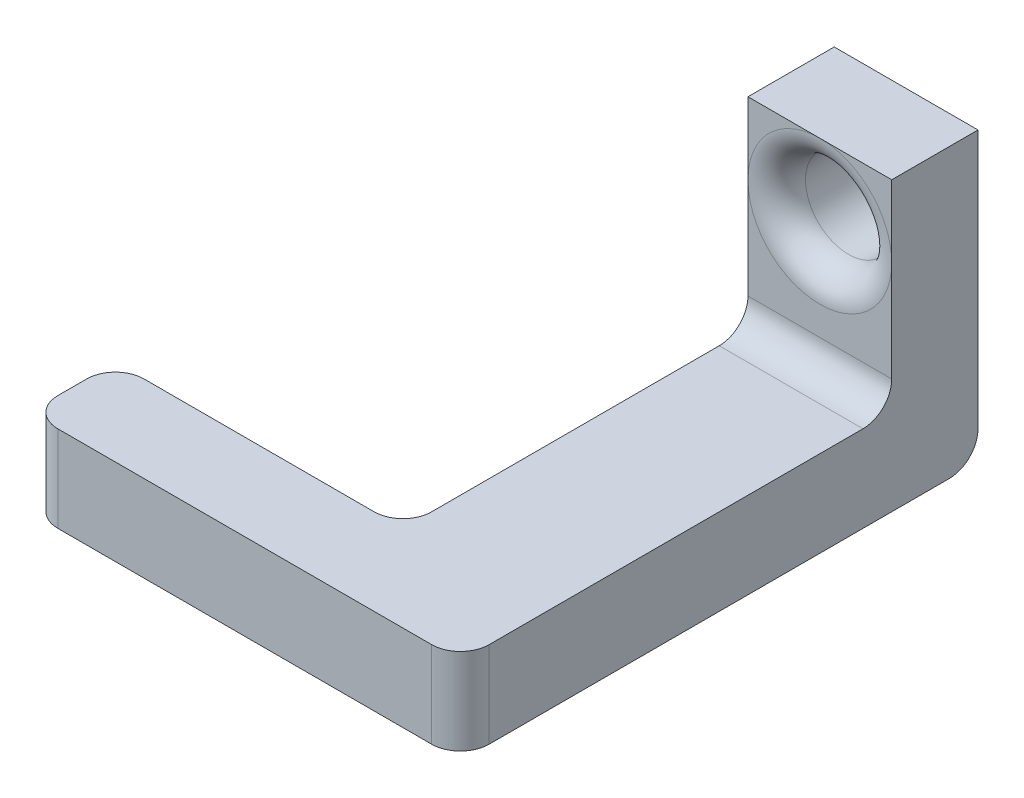
SolidWorks part; units mm, degrees
ref_plane "Front Plane" through (0, 0, 0) normal (0, 0, 1) x (1, 0, 0)
ref_plane "Top Plane" through (0, 0, 0) normal (0, 1, 0) x (1, 0, 0)
ref_plane "Right Plane" through (0, 0, 0) normal (1, 0, 0) x (0, 0, -1)
sketch "Sketch1" plane through (0, 0, 0) normal (0, 0, 1) x (1, 0, 0)
  line L1 (-6.901, 8.8281) -> (-1.901, 8.8281)
  line L2 (-6.901, 8.8281) -> (-6.901, -1.1719)
  line L3 (-6.901, -1.1719) -> (-1.901, -1.1719)
  line L4 (-1.901, 8.8281) -> (-1.901, -1.1719)
  circle A0 centre (-4.401, 6.3281) radius 1.5
  dimension "D3" = 3
  dimension "D4" = 2.5
  dimension "D1" = 5
  dimension "D2" = 10
extrude "Boss-Extrude1" add sketch "Sketch1" along normal blind 3
sketch "Sketch2" plane through (0, 0, 3) normal (0, 0, 1) x (1, 0, 0)
  line L0 (-1.901, -1.1719) -> (-1.901, 8.8281) construction
  line L1 (-6.901, -1.1719) -> (-1.901, -1.1719)
  line L2 (-6.901, -1.1719) -> (-6.901, 1.8281)
  line L3 (-6.901, 1.8281) -> (-1.901, 1.8281)
  line L4 (-1.901, -1.1719) -> (-1.901, 1.8281)
  dimension "D1" = 3
extrude "Boss-Extrude2" add sketch "Sketch2" along normal blind 15
sketch "Sketch3" plane through (-6.901, 0, 0) normal (-1, 0, 0) x (0, 0, 1)
  line L0 (18, -1.1719) -> (0, -1.1719) construction
  line L1 (18, 1.8281) -> (15, 1.8281)
  line L2 (18, 1.8281) -> (18, -1.1719)
  line L3 (18, -1.1719) -> (15, -1.1719)
  line L4 (15, 1.8281) -> (15, -1.1719)
  dimension "D1" = 3
extrude "Boss-Extrude3" add sketch "Sketch3" along normal blind 10
fillet "Fillet1" radius 1 1 edges
fillet "Fillet2" radius 1 1 edges at (-1.901, 0.3281, 18)
fillet "Fillet3" radius 1 1 edges at (-16.901, 0.3281, 15)
fillet "Fillet4" radius 1 1 edges at (-16.901, 0.3281, 18)
fillet "Fillet5" radius 1 1 edges at (-2.901, 6.3281, 3)
fillet "Fillet6" radius 1 1 edges at (-4.401, -1.1719, 0)
fillet "Fillet7" radius 1 1 edges
